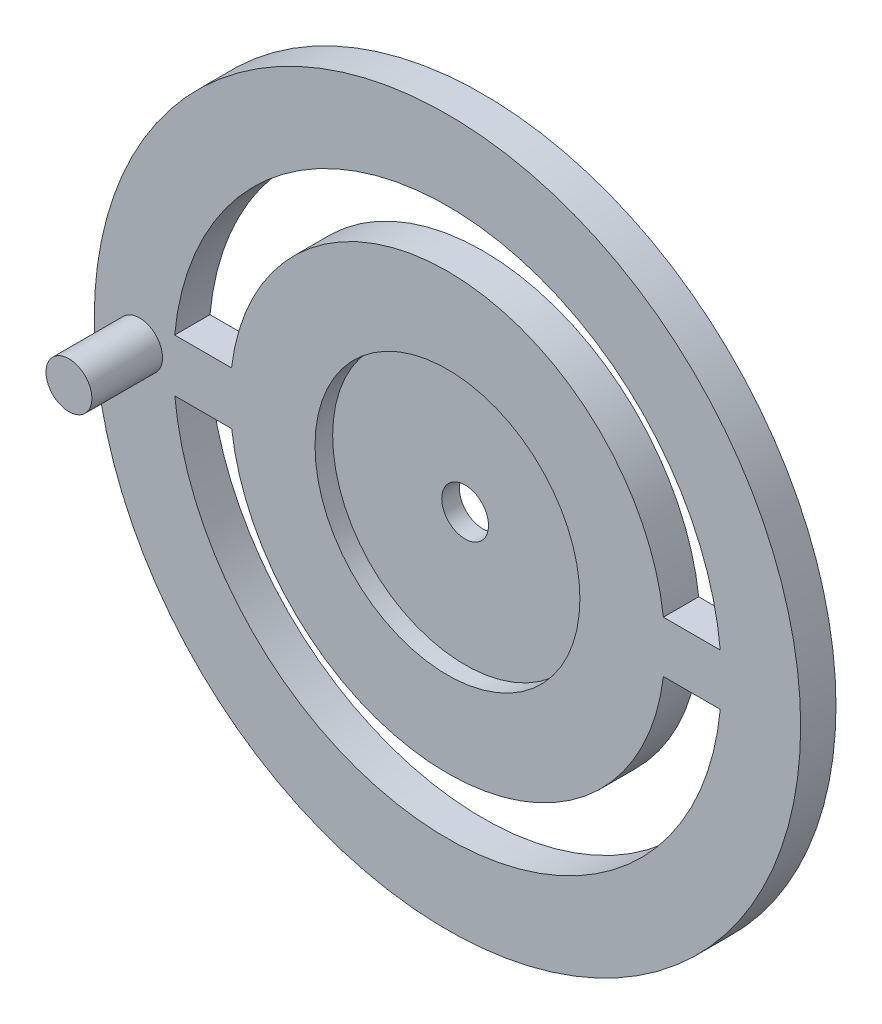
SolidWorks part; units mm, degrees
ref_plane "Front Plane" through (0, 0, 0) normal (0, 0, 1) x (1, 0, 0)
ref_plane "Top Plane" through (0, 0, 0) normal (0, 1, 0) x (1, 0, 0)
ref_plane "Right Plane" through (0, 0, 0) normal (1, 0, 0) x (0, 0, -1)
sketch "Sketch1" plane through (0, 0, 0) normal (0, 0, 1) x (1, 0, 0)
  line L18 (638.7672, -1252.1288) -> (632.3273, -1252.1288)
  line L22 (638.7843, -1258.0849) -> (632.3406, -1258.0832)
  line L24 (694.1108, -1252.1288) -> (687.6709, -1252.1288)
  line L26 (694.1108, -1257.9447) -> (687.6709, -1257.9447)
  circle A1 centre (663.219, -1255.0367) radius 40
  circle A11 centre (663.219, -1255.0367) radius 2.65
  arc A21 (632.3406, -1258.0832) -> (694.1108, -1257.9447) centre (663.219, -1255.0367) ccw
  arc A22 (638.7843, -1258.0849) -> (687.6709, -1257.9447) centre (663.219, -1255.0367) ccw
  arc A23 (687.6709, -1252.1288) -> (638.7672, -1252.1288) centre (663.219, -1255.0367) ccw
  arc A24 (694.1108, -1252.1288) -> (632.3273, -1252.1288) centre (663.219, -1255.0367) ccw
  point P0 (632.3273, -1258.0849)
  dimension "D1" = 80
extrude "Boss-Extrude1" add sketch "Sketch1" along normal blind 4
sketch "Sketch2" plane through (0, 0, 4) normal (0, 0, 1) x (1, 0, 0)
  line L0 (623.219, -1255.0367) -> (703.219, -1255.0367) construction
  circle A0 centre (663.219, -1255.0367) radius 40 construction
  circle A2 centre (628.3521, -1255.0367) radius 2.6
  point P7 (0, 0)
  point P8 (628.3521, -1255.0367)
  dimension "D1" = 5.2
extrude "Boss-Extrude2" add sketch "Sketch2" along normal blind 8
sketch "Sketch3" plane through (0, 0, 0) normal (0, 0, -1) x (-1, 0, 0)
  circle A0 centre (-663.219, -1255.0367) radius 15
  dimension "D1" = 30
extrude "Cut-Extrude2" cut sketch "Sketch3" against normal blind 10 from offset 2 offset against normal yes
